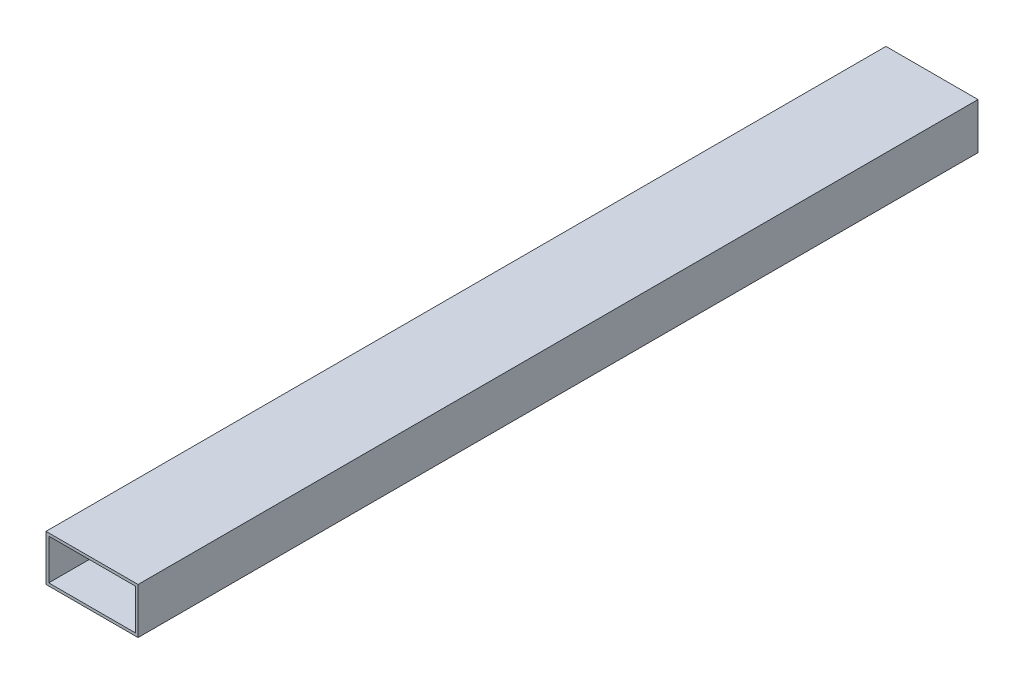
SolidWorks part; units mm, degrees
ref_plane "Front Plane" through (0, 0, 0) normal (0, 0, 1) x (1, 0, 0)
ref_plane "Top Plane" through (0, 0, 0) normal (0, 1, 0) x (1, 0, 0)
ref_plane "Right Plane" through (0, 0, 0) normal (1, 0, 0) x (0, 0, -1)
sketch "Sketch1" plane through (0, 0, 0) normal (0, 0, 1) x (1, 0, 0)
  line L1 (0, 0) -> (-50.8, 0)
  line L2 (0, 0) -> (0, 25.4)
  line L3 (0, 25.4) -> (-50.8, 25.4)
  line L4 (-50.8, 0) -> (-50.8, 25.4)
  dimension "D1" = 50.8
  dimension "D2" = 25.4
extrude "Extrude-Thin1" add sketch "Sketch1" along normal blind 463.55 thin thin type one direction reverse wall 1.524
